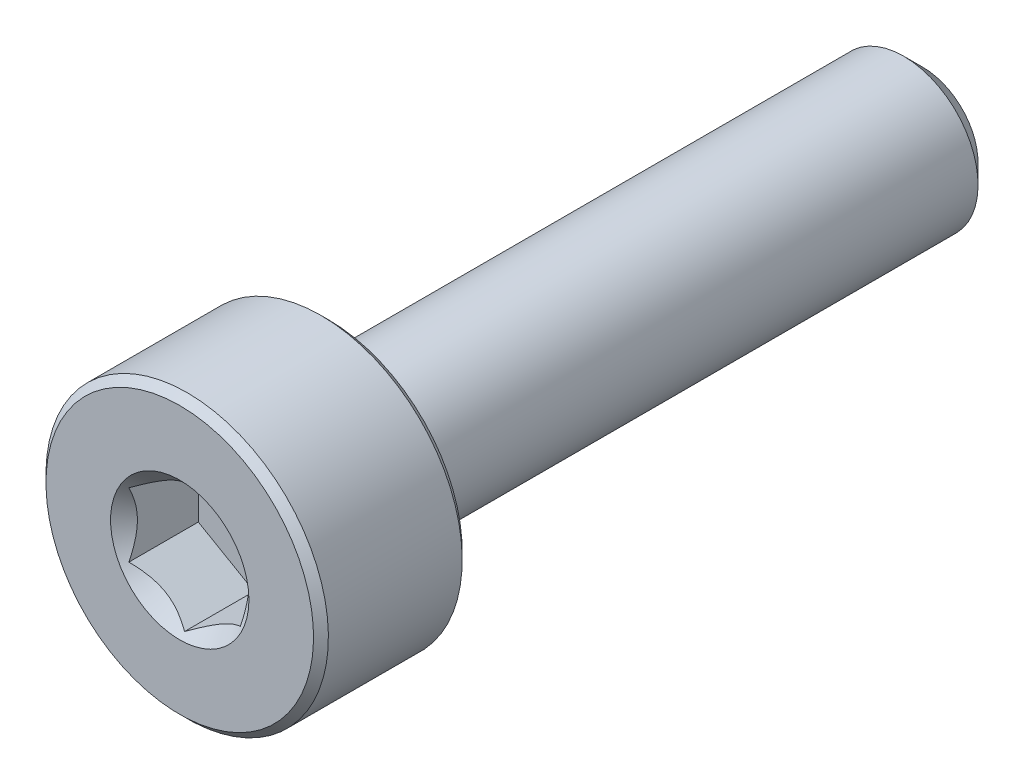
SolidWorks part; units mm, degrees
material "Alloy Steel (SS)"
ref_plane "Front Plane" through (0, 0, 0) normal (0, 0, 1) x (1, 0, 0)
ref_plane "Top Plane" through (0, 0, 0) normal (0, 1, 0) x (1, 0, 0)
ref_plane "Right Plane" through (0, 0, 0) normal (1, 0, 0) x (0, 0, -1)
sketch "Sketch1" plane through (0, 0, 0) normal (1, 0, 0) x (0, 0, -1)
  line L0 (-5, 0) -> (5, 0) construction
  line L1 (5, 0) -> (5, 0.7402) construction
  line L2 (5, 0.7402) -> (4.7402, 1) construction
  line L3 (4.7402, 1) -> (4.7, 1) construction
  line L4 (4.7, 1) -> (-3, 1) construction
  line L5 (-3, 1) -> (-3, 1.9) construction
  line L6 (-3, 1.9) -> (-5, 1.9) construction
  line L7 (-5, 1.9) -> (-5, 0) construction
  line L8 (5, 0.7402) -> (5, 1) construction
  line L9 (4.975, 1.0433) -> (5.175, 0.6969) construction
  line L10 (5.175, 0.6969) -> (5.375, 1.0433) construction
  line L11 (5.375, 1.0433) -> (4.975, 1.0433) construction
  line L12 (5.175, 1.0433) -> (5.175, 1) construction
  line L13 (5.175, 0.6969) -> (5.175, 0.7402) construction
  line L14 (5.15, 0.7402) -> (5.2, 0.7402) construction
  line L15 (5, 1) -> (5.35, 1) construction
  line L16 (4.9875, 1.0217) -> (5.3625, 1.0217) construction
  line L17 (5, 0) -> (5, -1) construction
  line L18 (-3.1, 1.9) -> (-3, 1.8) construction
  line L19 (-4.9, 1.9) -> (-5, 1.8) construction
  line L20 (-3, 1) -> (-3, 0) construction
  line L21 (-3, 0.5) -> (-0.3333, 0.5) construction
  line L22 (-0.3333, 0.5) -> (2.3333, 0.5) construction
  line L23 (2.3333, 0.5) -> (5, 0.5) construction
  line L24 (-0.3333, 0.5) -> (-0.3333, 1) construction
  line L25 (-0.3333, 1) -> (-0.3333, 1.9) construction
  line L26 (2.3333, 0.5) -> (2.3333, 1.9) construction
  point P0 (-5, 0.75)
  point P3 (4, 1)
  point P4 (0, 0)
  point P18 (2.3333, 1)
  point P22 (5.175, 0.7402)
  point P24 (4.7, 1)
  point P25 (5.175, 1)
  point P28 (5.175, 1.0217)
  point P29 (4, -1)
  point P30 (-0.3333, 1)
  point P31 (-4, 1.9)
  point P37 (-3.35, 1.9)
  point P38 (-4.85, 1.9)
  point P45 (-0.3333, 0.5)
  point P46 (2.3333, 0.5)
  dimension "D2" = 0.05
  dimension "D7" = 0.1
  dimension "D8" = 0.1
  dimension "D9" = 0.1
  dimension "D10" = 0.05
  dimension "D11" = 0.25
  dimension "Drive Size" = 1.5
  dimension "Head Diameter" = 3.8
  dimension "Head Height" = 2
  dimension "Thread Pitch" = 0.4
  dimension "Thread Dia" = 2
  dimension "Length" = 8
  dimension "D12" = 0.3
  dimension "D4" = 1
  dimension "D3" = 45
sketch "Sketch2" plane through (0, 0, 0) normal (1, 0, 0) x (0, 0, -1)
  line L0 (-5, 0) -> (-5, 1.8)
  line L1 (-4.9, 1.9) -> (-3.1, 1.9)
  line L2 (-3, 1.8) -> (-3, 1.1)
  line L4 (4.7402, 1) -> (5, 0.7402)
  line L5 (5, 0.7402) -> (5, 0)
  line L6 (-3, 1.9) -> (-5, 1.9) construction
  line L7 (5, 0) -> (-5, 0)
  line L8 (-4.9, 1.9) -> (-5, 1.8) construction
  line L10 (-4.9, 1.9) -> (-5, 1.8)
  line L14 (-3.1, 1.9) -> (-3, 1.8) construction
  line L16 (-3.1, 1.9) -> (-3, 1.8)
  line L17 (-3, 1) -> (-3, 1.9) construction
  line L19 (-2.9, 1) -> (4.7402, 1)
  line L20 (4.7, 1) -> (-3, 1) construction
  arc A1 (-3, 1.1) -> (-2.9, 1) centre (-2.9, 1.1) ccw
  dimension "D3" = 0.1
revolve "Revolve1" add sketch "Sketch2" angle 360 about L7
sketch "Sketch3" plane through (0, 0, 5) normal (0, 0, 1) x (1, 0, 0)
  line L1 (0.75, -0.433) -> (0.75, 0.433)
  line L2 (0.75, 0.433) -> (0, 0.866)
  line L3 (0, 0.866) -> (-0.75, 0.433)
  line L4 (-0.75, 0.433) -> (-0.75, -0.433)
  line L5 (-0.75, -0.433) -> (0, -0.866)
  line L6 (0, -0.866) -> (0.75, -0.433)
  circle A0 centre (0, 0) radius 0.75 construction
  circle A1 centre (0, 0) radius 1.9 construction
  circle A2 centre (0, 0) radius 1.9 construction
  circle A3 centre (0, 0) radius 0.866 construction
  point P13 (0, 0)
  dimension "D1" = 1.7321
extrude "Cut-Extrude1" cut sketch "Sketch3" against normal offset from surface (1 mm away) 1 up to face at (0, 1.8, 3)
sketch "Sketch4" plane through (0, 0, 5) normal (0, 0, 1) x (1, 0, 0)
  circle A0 centre (0, 0) radius 0.931
  dimension "D1" = 1.862
extrude "Cut-Extrude2" cut sketch "Sketch4" against normal up to vertex (1 mm away) draft 45 up to point (0, 1.9, 4)
sketch "Sketch11" plane through (0, 0, 0) normal (1, 0, 0) x (0, 0, -1)
  line L0 (-5, 0) -> (5, 0) construction
  line L1 (-5, 0) -> (5, 0) construction
  line L2 (-1.5, 0) -> (-1.5, 1) construction
  line L3 (4.7, 1) -> (-3, 1) construction
  line L4 (3.5, 0) -> (3.5, 1) construction
  line L6 (5, 0.7402) -> (5, 1) construction
  point P2 (-1.5, 0)
  point P3 (3.5, 0)
  dimension "D1" = 1.5
  dimension "D2" = 1.5
sketch "Sketch6" [suppressed] plane through (0, 0, -5) normal (0, 0, -1) x (-1, 0, 0)
  circle A0 centre (0, 0) radius 1
curve "Helix/Spiral1" [suppressed] pitch 0.4 height 8.4 turns 21
sketch "Sketch10" [suppressed] plane through (0, 0, 0) normal (1, 0, 0) x (0, 0, -1)
  line L0 (-2.9, -1.9) -> (-2.9, 1.9)
  line L5 (-5, 0) -> (5, 0) construction
  line L6 (-2.9, 1) -> (-2.9, -1) construction
  point P3 (-2.9, 0)
split "Split1" [suppressed] bodies to split 106
sketch "Sketch7" [suppressed] plane through (0, 0, 0) normal (1, 0, 0) x (0, 0, -1)
  line L0 (4.9875, 1.0217) -> (5.3625, 1.0217)
  line L1 (5.3625, 1.0217) -> (5.2, 0.7402)
  line L2 (5.2, 0.7402) -> (5.15, 0.7402)
  line L3 (5.15, 0.7402) -> (4.9875, 1.0217)
sweep "Cut-Sweep1" [suppressed] cut profiles "Sketch7" path "Helix/Spiral1"
sketch "Sketch8" [suppressed] plane through (0, 0, 0) normal (1, 0, 0) x (0, 0, -1)
  line L0 (-3, 0) -> (-3, 1)
  line L1 (-2.9, -1) -> (-2.9, 1) construction
  line L2 (-3, 1) -> (-2.9, 1)
  line L4 (-2.9, 1) -> (-2.3226, 0)
  line L5 (-2.3226, 0) -> (-3, 0)
  line L6 (4.7, 1) -> (-3, 1) construction
  line L7 (-5, 0) -> (5, 0) construction
  dimension "D1" = 60
revolve "Revolve2" [suppressed] add sketch "Sketch8" angle 360 about L5
equation "\"D2@Sketch1\" = \"Thread Pitch@Sketch1\" / 8"
equation "\"D4@Helix/Spiral1\" = \"Thread Pitch@Sketch1\""
equation "\"D7@Sketch1\" = \"Head Height@Sketch1\" * .05"
equation "\"D8@Sketch1\"=\"D7@Sketch1\""
equation "\"D9@Sketch1\"=\"D7@Sketch1\""
equation "\"D10@Sketch1\"=\"D7@Sketch1\"/2"
equation "\"D11@Sketch1\"=\"D10@Sketch1\"*5"
equation "\"D4@Sketch1\"=\"Thread Pitch@Sketch1\"*2.5"
equation "\"D12@Sketch1\"=\"Thread Pitch@Sketch1\"*.75"
equation "\"D3@Helix/Spiral1\"=\"Length@Sketch1\"+\"Thread Pitch@Sketch1\""
equation "\"D3@Sketch2\"=\"Thread Dia@Sketch1\"*0.05"
equation "\"D1@Sketch11\"=\"Length@Sketch1\"*0.1875"
equation "\"D2@Sketch11\"=\"D1@Sketch11\""
equation "\"D1@Sketch4\"=\"D1@Sketch3\"*1.075"
